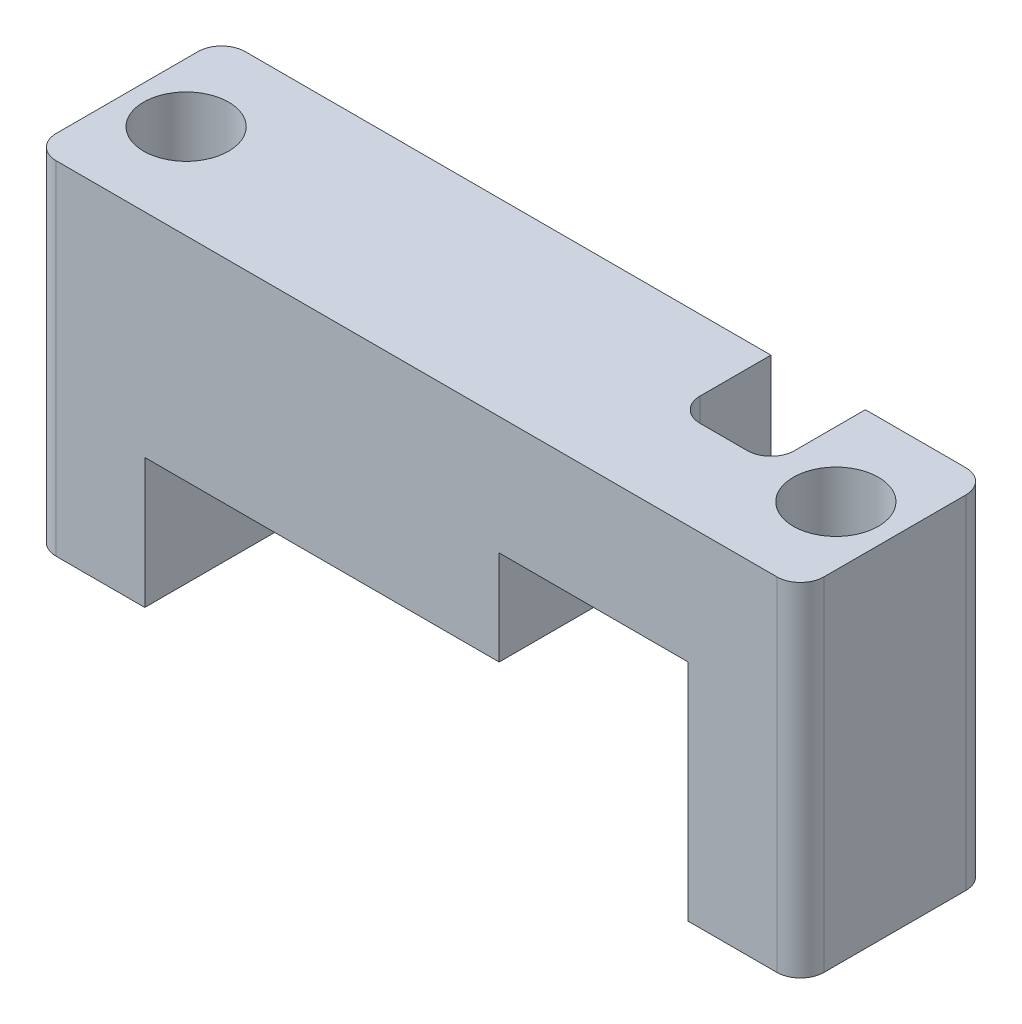
SolidWorks part; units mm, degrees
ref_plane "Front Plane" through (0, 0, 0) normal (0, 0, 1) x (1, 0, 0)
ref_plane "Top Plane" through (0, 0, 0) normal (0, 1, 0) x (1, 0, 0)
ref_plane "Right Plane" through (0, 0, 0) normal (1, 0, 0) x (0, 0, -1)
sketch "Sketch1" plane through (0, 0, 0) normal (0, 0, 1) x (1, 0, 0)
  line L0 (-16.25, -5.5) -> (-11.5, -5.5)
  line L1 (-11.5, -5.5) -> (-11.5, 0)
  line L2 (-11.5, 0) -> (3.5, 0)
  line L3 (3.5, 0) -> (3.5, 4)
  line L4 (3.5, 4) -> (11.5, 4)
  line L5 (11.5, 4) -> (11.5, -5.5)
  line L6 (11.5, -5.5) -> (16.25, -5.5)
  line L7 (16.25, -5.5) -> (16.25, 9)
  line L8 (16.25, 9) -> (-16.25, 9)
  line L9 (-16.25, 9) -> (-16.25, -5.5)
  point P10 (0, 9)
  dimension "D1" = 23
  dimension "D2" = 32.5
  dimension "D3" = 3.5
  dimension "D4" = 4
  dimension "D5" = 5.5
  dimension "D6" = 5
extrude "Boss-Extrude1" add sketch "Sketch1" along normal blind 8 contours L8 L9 L0 L1 L2 L3 L4 L5 L6 L7
hole_wizard "M3 Clearance Hole1" positions "Sketch2" profile "Sketch4" hole size "M3" standard "ISO" end condition up to next
sketch "Sketch2" plane through (0, 9, 0) normal (0, 1, 0) x (1, 0, 0)
  line L0 (-16.25, -8) -> (-16.25, 0) construction
  line L1 (13.75, -4) -> (-13.75, -4)
  line L3 (16.25, 0) -> (-16.25, 0) construction
  point P0 (13.75, -4)
  point P2 (-13.75, -4)
  point P7 (-16.25, -4)
  point P12 (0, -4)
  point P15 (0, 0)
  dimension "D1" = 27.5
sketch "Sketch4" plane through (13.75, 9, 4) normal (1, 0, 0) x (0, 0, 1)
  line L0 (0, 0) -> (0, 14.5)
  line L1 (0, 14.5) -> (1.8, 14.5)
  line L2 (1.8, 14.5) -> (1.8, 0)
  line L5 (1.8, 0) -> (0, 0)
  line L11 (0, -6.35) -> (0, 107.95) construction
  dimension "Thru Hole Dia." = 3.6
  dimension "Thru Hole Depth" = 14.5
fillet "Fillet1" radius 1 4 edges at (16.25, 1.75, 0) (16.25, 1.75, 8) (-16.25, 1.75, 0) (-16.25, 1.75, 8)
sketch "Sketch5" plane through (0, 0, 0) normal (0, 0, -1) x (-1, 0, 0)
  line L0 (-15.25, 9) -> (15.25, 9) construction
  line L1 (-11, 9) -> (-7, 9)
  line L2 (-11, 9) -> (-11, 0)
  line L3 (-11, 0) -> (-7, 0)
  line L4 (-7, 9) -> (-7, 0)
  line L6 (11.5, 0) -> (-3.5, 0) construction
  line L9 (-11.5, 4) -> (-11.5, -5.5) construction
  dimension "D1" = 4
  dimension "D2" = 0.5
extrude "Cut-Extrude1" cut sketch "Sketch5" against normal blind 4
fillet "Fillet2" radius 1 2 edges at (11, 6.5, 4) (7, 6.5, 4)
other "Freeze***"
